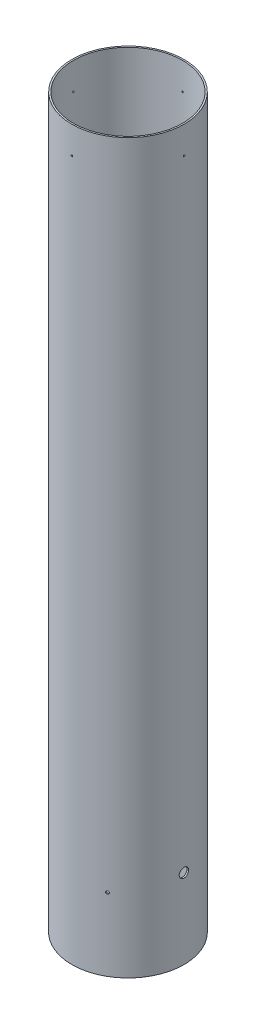
SolidWorks part; units mm, degrees
material "A-Glass Fiber"
ref_plane "Front Plane" through (0, 0, 0) normal (0, 0, 1) x (1, 0, 0)
ref_plane "Top Plane" through (0, 0, 0) normal (0, 1, 0) x (1, 0, 0)
ref_plane "Right Plane" through (0, 0, 0) normal (1, 0, 0) x (0, 0, -1)
sketch "Sketch1" plane through (0, 0, 0) normal (0, 1, 0) x (1, 0, 0)
  circle A0 centre (0, 0) radius 76.1746
  circle A1 centre (0, 0) radius 78.359
  dimension "D1" = 156.718
  dimension "D2" = 152.3492
extrude "Boss-Extrude1" add sketch "Sketch1" along normal blind 1016
ref_axis "Axis1" through (0, 1016, 0) along (0, -1, 0)
sketch "Sketch2" plane through (0, 0, 0) normal (1, 0, 0) x (0, 0, -1)
  line L0 (78.359, 1016) -> (-78.359, 1016) construction
  circle A0 centre (0, 977.9) radius 1.0922
  dimension "D1" = 2.1844
  dimension "D2" = 38.1
extrude "Cut-Extrude1" cut sketch "Sketch2" against normal through all
pattern_circular "CirPattern1" count 4 over 360 about axis through (0, 1016, 0) along (0, 1, 0) of "Cut-Extrude1"
hole_wizard "1/2 Clearance Hole1" positions "Sketch3" profile "Sketch4" hole size "1/2" standard "ANSI Inch"
sketch "Sketch3" plane through (0, 0, 0) normal (1, 0, 0) x (0, 0, -1)
  point P0 (0, 111.125)
  dimension "D1" = 111.125
sketch "Sketch4" plane through (0, 111.125, 0) normal (0, 1, 0) x (0, 0, 1)
  line L0 (0, 0) -> (0, 92.8345)
  line L1 (0, 92.8345) -> (6.5481, 88.9)
  line L2 (6.5481, 88.9) -> (6.5481, 0)
  line L5 (6.5481, 0) -> (0, 0)
  line L10 (0, 92.8345) -> (-6.5481, 88.9) construction
  line L11 (0, -6.35) -> (0, 107.95) construction
  dimension "Hole Dia." = 13.0962
  dimension "Hole Depth" = 88.9
  dimension "Drill Angle" = 118
hole_wizard "Ø4.0 (4) Diameter Hole1" positions "Sketch5" profile "Sketch6" hole size "Ø4.0" standard "ANSI Metric"
sketch "Sketch5" plane through (0, 0, 0) normal (1, 0, 0) x (0, 0, -1)
  point P0 (0, 101.6)
  dimension "D1" = 101.6
sketch "Sketch6" plane through (0, 101.6, 0) normal (0, 1, 0) x (0, 0, -1)
  line L0 (0, 0) -> (0, 90.1017)
  line L1 (0, 90.1017) -> (2, 88.9)
  line L2 (2, 88.9) -> (2, 0)
  line L5 (2, 0) -> (0, 0)
  line L10 (0, 90.1017) -> (-2, 88.9) construction
  line L11 (0, -6.35) -> (0, 107.95) construction
  dimension "Hole Dia." = 4
  dimension "Hole Depth" = 88.9
  dimension "Drill Angle" = 118
pattern_circular "CirPattern2" count 3 over 360 about axis through (0, 0, 0) along (0, 1, 0) of "Ø4.0 (4) Diameter Hole1"
equation "\"Fwd_Tube_Length\"= 40in"
equation "\"D1@Boss-Extrude1\" = \"Fwd_Tube_Length\""
equation "\"BKHD_Screw_Diam\"= 3.5mm"
equation "\"Fwd_BKHD_From_Top\"= 18in"
equation "\"Bodytube_OD\"= 6.17in"
equation "\"Bodytube_ID\"= 5.998in"
equation "\"D2@Sketch1\"=\"Bodytube_ID\""
equation "\"D1@Sketch1\"=\"Bodytube_OD\""
equation "\"Shear_Screw_Diameter\"= 0.086in"
equation "\"Shear_Screw_Coupler_Location\"= 4.5in"
equation "\"Motor_OD\"= 4in"
equation "\"Mid_Tube_Length\"= 1in"
equation "\"Mid_Coupler_Length\"= 13in"
equation "\"Aft_Section_Length\"= 39in"
equation "\"AB_Coupler_OD_Length\"= 1in"
equation "\"AB_Coupling_Section_Length\"= 0.375in"
equation "\"AB_Coupler_Length\"= \"AB_Coupler_OD_Length\" + \"AB_Coupling_Section_Length\" * 2"
equation "\"Cutout_Angle\"= 80"
equation "\"AB_Paddle_Height\"= 0.375in"
equation "\"AB_Coupler_Num_Screws\"= 4"
equation "\"AB_BKHD_Thickness\"= 0.375in"
equation "\"AB_Mount_From_Bottom\"= 23.175in"
equation "\"Num_Cutouts\"= 3"
equation "\"AB_Coupler_OD\"= 6.17in"
equation "\"AB_Coupler_ID\"= 5.75in"
equation "\"AB_Coupler_Surface_Diameter\"= 5.998in"
equation "\"AB_Coupling_Screw_Diameter\"= 0.15748in"
equation "\"AB_Central_Bushing_Length\"= .4724in"
equation "\"Lead_Screw_Dist\"= 3.4in"
equation "\"Lead_Screw_Diam\"= 0.386in"
equation "\"Lead_Screw_Length\"= (\"Mid_Coupler_Length\" + 2*0.375in + 2*0.5in)"
equation "\"Paddle_Pin_Offset\"= .25in"
equation "\"Paddle_Pin_Radius\"= 2.25in"
equation "\"SS_Paddle_Pin_Radius\"= 2.25*0.66in"
equation "\"Paddle_Gear_OD\"= 3.2in"
equation "\"Drive_Gear_OD\"= 1.7in"
equation "\"Fin_Thickness\"= .118in"
equation "\"Guiderail_Cutout_Diameter\"= 1.5in"
equation "\"DB9_Hole_Dist\"= 25mm"
equation "\"DB9_Relief_Width\"= 0.47in"
equation "\"DB9_Relief_Hole_Offset\"= 0.09in"
equation "\"Airbrakes_Wire_Hole_Dia\"= .25in"
equation "\"Airbrakes_Wire_Hole_Dist\"= 1.1in"
equation "\"Servo_Gear_Offset\"= 0.5in"
equation "\"D1@Sketch2\"=\"Shear_Screw_Diameter\""
equation "\"FWD_Shear_Screw_Dist\"= 1.5in"
equation "\"D2@Sketch2\"=\"FWD_Shear_Screw_Dist\""
